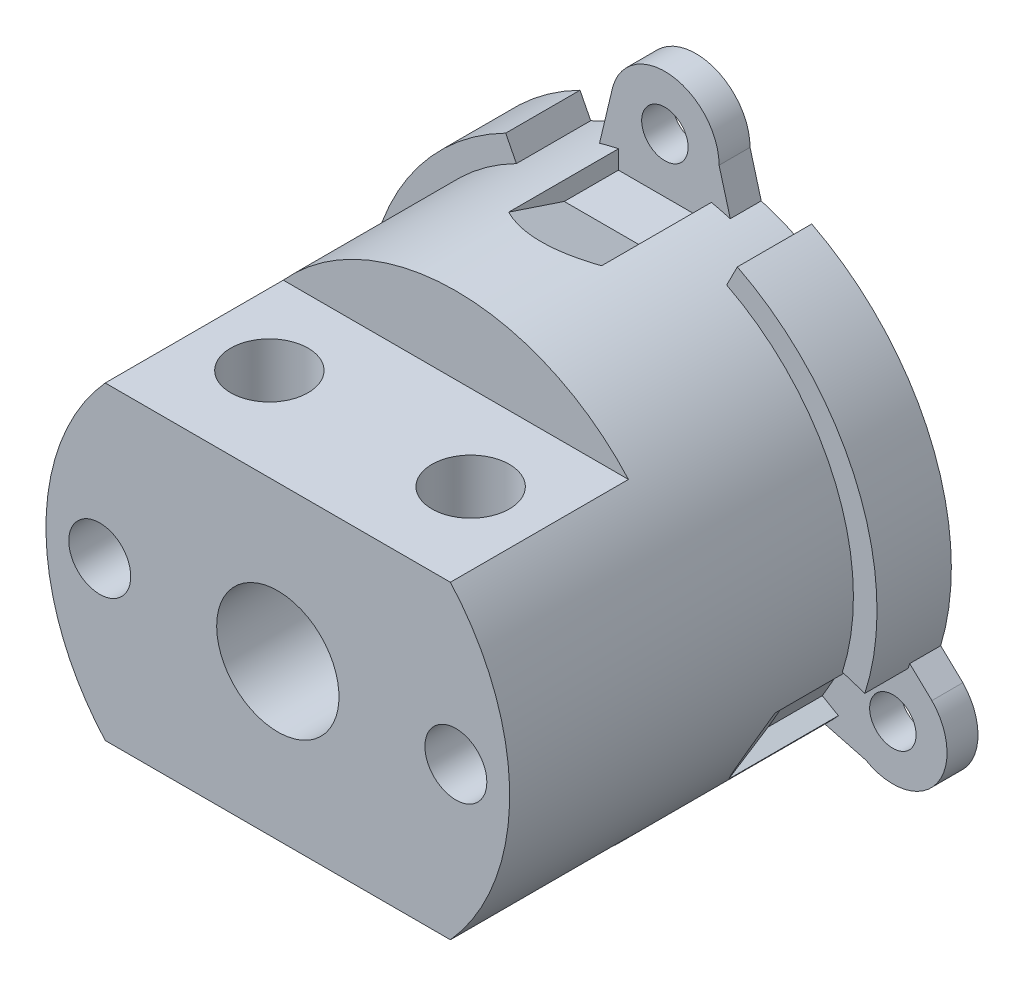
SolidWorks part; units mm, degrees
ref_plane "Front Plane" through (0, 0, 0) normal (0, 0, 1) x (1, 0, 0)
ref_plane "Top Plane" through (0, 0, 0) normal (0, 1, 0) x (1, 0, 0)
ref_plane "Right Plane" through (0, 0, 0) normal (1, 0, 0) x (0, 0, -1)
sketch "Sketch1" plane through (0, 0, 0) normal (0, 0, 1) x (1, 0, 0)
  circle A0 centre (0, 0) radius 14.975
  dimension "D1" = 29.95
extrude "Extrude1" add sketch "Sketch1" along normal blind 27
sketch "Sketch2" plane through (0, 0, 0) normal (0, 0, 1) x (1, 0, 0)
  line L0 (-3.3633, 17.9685) -> (-4.2216, 14.3676)
  line L1 (3.5, 17) -> (4.2216, 14.3676)
  line L2 (4.2216, 14.3676) -> (-4.2216, 14.3676)
  arc A0 (3.5, 17) -> (-3.3633, 17.9685) centre (0, 17) ccw
  circle A1 centre (0, 0) radius 14.975 construction
  circle A2 centre (0, 0) radius 14.975 construction
  point P8 (0, 14.3676)
  dimension "D1" = 3.5
  dimension "D2" = 17
extrude "Extrude2" add sketch "Sketch2" along normal blind 2
sketch "Sketch3" plane through (0, 0, 2) normal (0, 0, 1) x (1, 0, 0)
  circle A0 centre (0, 17) radius 1.5
  dimension "D1" = 3
  dimension "D2" = 17
extrude "Extrude3" cut sketch "Sketch3" against normal blind 3
sketch "Sketch4" plane through (0, 0, 0) normal (1, 0, 0) x (0, 0, -1)
  line L0 (-2, 14.975) -> (-2, 13.475)
  line L1 (-2, 13.475) -> (-5.5, 13.475)
  line L2 (-5.5, 13.475) -> (-10, 14.975)
  line L3 (-2, 14.975) -> (-27, 14.975) construction
  line L4 (-10, 14.975) -> (-2, 14.975)
  dimension "D1" = 8
  dimension "D2" = 3.5
  dimension "D3" = 1.5
extrude "Extrude6" cut sketch "Sketch4" against normal blind 3 and the other way blind 3
pattern_circular "CirPattern1" count 3 over 360 about axis through (0, 0, 0) along (0, 0, 1) of "Extrude2", "Extrude3", "Extrude6"
sketch "Sketch5" plane through (0, 0, 27) normal (0, 0, 1) x (1, 0, 0)
  line L0 (0, 0) -> (0, 14.975) construction
  line L1 (-16.5653, 19.7627) -> (20.5541, 19.7627)
  line L2 (-16.5653, 19.7627) -> (-16.5653, 10)
  line L3 (-16.5653, 10) -> (20.5541, 10)
  line L4 (20.5541, 19.7627) -> (20.5541, 10)
  circle A0 centre (0, 0) radius 14.975 construction
  dimension "D1" = 10
extrude "Extrude7" cut sketch "Sketch5" against normal blind 11.5
mirror "Mirror2" about plane through (0, 0, 0) normal (0, 1, 0) of "Extrude7"
sketch "Sketch6" plane through (0, -10, 0) normal (0, -1, 0) x (1, 0, 0)
  line L0 (-6.5458, 21) -> (6.4542, 21) construction
  line L1 (-0.0458, 21) -> (0, 27) construction
  line L3 (-11.1468, 27) -> (11.1468, 27) construction
  circle A0 centre (-6.5458, 21) radius 2.5
  circle A1 centre (6.4542, 21) radius 2.5
  dimension "D1" = 5
  dimension "D2" = 6
  dimension "D4" = 13
extrude "Extrude8" cut sketch "Sketch6" against normal through all
sketch "Sketch7" plane through (0, 0, 0) normal (0, 0, -1) x (-1, 0, 0)
  circle A0 centre (0, 0) radius 3.95
  dimension "D1" = 7.9
extrude "Extrude9" cut sketch "Sketch7" against normal through all
hole_wizard "Ø4.0 (4) Diameter Hole1" positions "3DSketch1" profile "Sketch8" hole size "Ø4.0" standard "Ansi Metric"
sketch3d "3DSketch1"
  line L0 (-11.5, -0.0016, 27) -> (11.5, -0.0016, 27) construction
  line L3 (0, -0.0016, 27) -> (0, 10, 27) construction
  line L4 (-11.1468, 10, 27) -> (11.1468, 10, 27) construction
  point P0 (-11.5, -0.0016, 27)
  point P2 (11.5, -0.0016, 27)
  dimension "D1" = 23
sketch "Sketch8" plane through (-11.5, -0.0016, 27) normal (1, 0, 0) x (0, -1, 0)
  line L0 (0, 0) -> (0, 15)
  line L1 (0, 15) -> (2, 15)
  line L2 (2, 15) -> (2, 0)
  line L5 (2, 0) -> (0, 0)
  line L10 (0, 15) -> (-2, 15) construction
  line L11 (0, -6.35) -> (0, 107.95) construction
  dimension "Hole Dia." = 4
  dimension "Hole Depth" = 15
  dimension "Drill Angle" = 180
sketch "Sketch9" plane through (0, 0, 0) normal (0, 0, 1) x (1, 0, 0)
  line L0 (-7.4821, 14.7061) -> (-6.7905, 13.3469)
  line L1 (7.4821, 14.7061) -> (6.7905, 13.3469)
  line L2 (-15.7137, -5.0329) -> (-14.2058, -4.7376)
  line L3 (15.7137, -5.0329) -> (14.2614, -4.5678)
  arc A0 (-7.4821, 14.7061) -> (-15.7137, -5.0329) centre (0, 0) ccw
  arc A1 (-6.7905, 13.3469) -> (-14.2058, -4.7376) centre (0, 0) ccw
  arc A2 (11.1468, 10) -> (-11.1468, 10) centre (0, 0) ccw construction
  arc A3 (14.5535, -3.5278) -> (4.2216, 14.3676) centre (0, 0) ccw construction
  arc A4 (14.2614, -4.5678) -> (6.7905, 13.3469) centre (0, 0) ccw
  arc A5 (15.7137, -5.0329) -> (7.4821, 14.7061) centre (0, 0) ccw
  dimension "D1" = 33
extrude "Extrude10" add sketch "Sketch9" along normal blind 4.8
